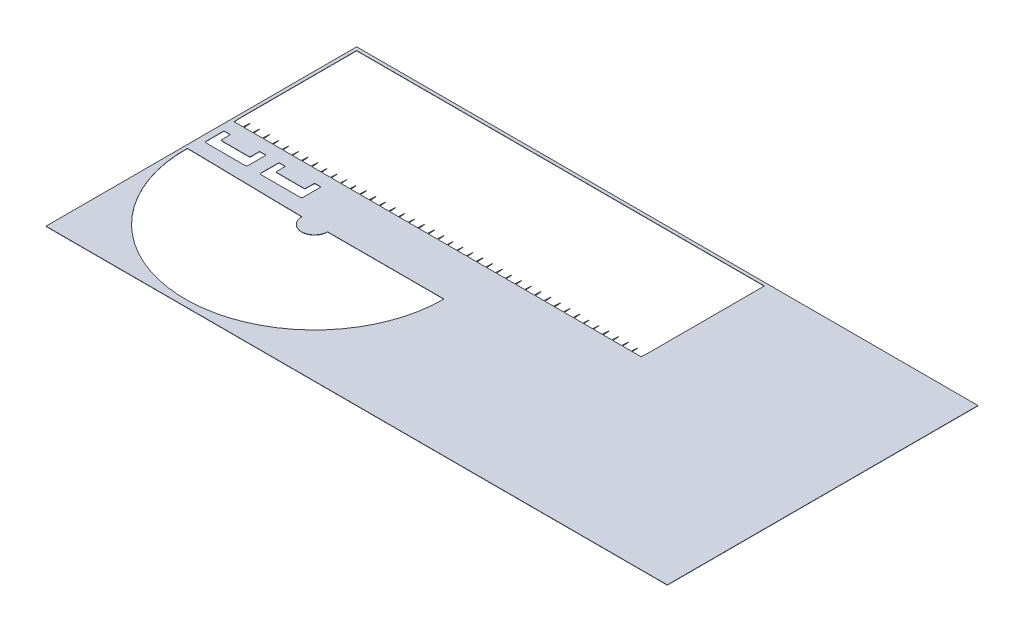
SolidWorks part; units mm, degrees
ref_plane "Front Plane" through (0, 0, 0) normal (0, 0, 1) x (1, 0, 0)
ref_plane "Top Plane" through (0, 0, 0) normal (0, 1, 0) x (1, 0, 0)
ref_plane "Right Plane" through (0, 0, 0) normal (1, 0, 0) x (0, 0, -1)
sketch "Sketch1" plane through (0, 0, 0) normal (0, 1, 0) x (1, 0, 0)
  line L1 (-1219.2, 609.6) -> (1219.2, 609.6)
  line L2 (-1219.2, 609.6) -> (-1219.2, -609.6)
  line L3 (-1219.2, -609.6) -> (1219.2, -609.6)
  line L4 (1219.2, 609.6) -> (1219.2, -609.6)
  line L5 (-1219.2, 609.6) -> (1219.2, -609.6) construction
  line L6 (-1219.2, -609.6) -> (1219.2, 609.6) construction
  point P0 (0, 0)
  dimension "D1" = 1219.2
  dimension "D2" = 2438.4
base flange "Base-Flange1" sketch "Sketch1" thickness 1.0236 reverse thickness direction no parameters "D1"=0.7366
sketch "Sketch6" plane through (0, 0, 0) normal (0, 1, 0) x (1, 0, 0)
  line L0 (1219.2, 609.6) -> (-1219.2, 609.6) construction
  line L1 (-1206.5, 596.9) -> (393.7, 596.9)
  line L2 (-1206.5, 596.9) -> (-1206.5, 139.7)
  line L3 (-1206.5, 139.7) -> (-1204.6839, 114.3)
  line L4 (393.7, 596.9) -> (393.7, 139.7)
  line L5 (-1219.2, 609.6) -> (-1219.2, -609.6) construction
  line L6 (-647.7, -76.2) -> (-190.5, -76.2)
  line L7 (-1206.4226, -67.3342) -> (-749.2923, -75.3134)
  line L8 (-1204.6839, 114.3) -> (-1170.2161, 114.3)
  line L9 (-1170.2161, 114.3) -> (-1168.4, 139.7)
  line L10 (-1168.4, 139.7) -> (-1206.5, 139.7) construction
  line L11 (-1187.45, 139.7) -> (-1187.45, 114.3) construction
  line L12 (-1111.25, -12.7) -> (-1187.45, -12.7)
  line L13 (-1168.4, 139.7) -> (-1166.5839, 114.3)
  line L14 (-1166.5839, 114.3) -> (-1132.1161, 114.3)
  line L15 (-1132.1161, 114.3) -> (-1130.3, 139.7)
  line L16 (-1130.3, 139.7) -> (-1128.4839, 114.3)
  line L17 (-1128.4839, 114.3) -> (-1094.0161, 114.3)
  line L18 (-1094.0161, 114.3) -> (-1092.2, 139.7)
  line L19 (-1092.2, 139.7) -> (-1090.3839, 114.3)
  line L20 (-1090.3839, 114.3) -> (-1055.9161, 114.3)
  line L21 (-1055.9161, 114.3) -> (-1054.1, 139.7)
  line L22 (-1054.1, 139.7) -> (-1052.2839, 114.3)
  line L23 (-1052.2839, 114.3) -> (-1017.8161, 114.3)
  line L24 (-1017.8161, 114.3) -> (-1016, 139.7)
  line L25 (-1016, 139.7) -> (-1014.1839, 114.3)
  line L26 (-1014.1839, 114.3) -> (-979.7161, 114.3)
  line L27 (-979.7161, 114.3) -> (-977.9, 139.7)
  line L28 (-977.9, 139.7) -> (-976.0839, 114.3)
  line L29 (-976.0839, 114.3) -> (-941.6161, 114.3)
  line L30 (-941.6161, 114.3) -> (-939.8, 139.7)
  line L31 (-939.8, 139.7) -> (-937.9839, 114.3)
  line L32 (-937.9839, 114.3) -> (-903.5161, 114.3)
  line L33 (-903.5161, 114.3) -> (-901.7, 139.7)
  line L34 (-901.7, 139.7) -> (-899.8839, 114.3)
  line L35 (-899.8839, 114.3) -> (-865.4161, 114.3)
  line L36 (-865.4161, 114.3) -> (-863.6, 139.7)
  line L37 (-863.6, 139.7) -> (-861.7839, 114.3)
  line L38 (-861.7839, 114.3) -> (-827.3161, 114.3)
  line L39 (-827.3161, 114.3) -> (-825.5, 139.7)
  line L40 (-825.5, 139.7) -> (-823.6839, 114.3)
  line L41 (-823.6839, 114.3) -> (-789.2161, 114.3)
  line L42 (-789.2161, 114.3) -> (-787.4, 139.7)
  line L43 (-787.4, 139.7) -> (-785.5839, 114.3)
  line L44 (-785.5839, 114.3) -> (-751.1161, 114.3)
  line L45 (-751.1161, 114.3) -> (-749.3, 139.7)
  line L46 (-749.3, 139.7) -> (-747.4839, 114.3)
  line L47 (-747.4839, 114.3) -> (-713.0161, 114.3)
  line L48 (-713.0161, 114.3) -> (-711.2, 139.7)
  line L49 (-711.2, 139.7) -> (-709.3839, 114.3)
  line L50 (-709.3839, 114.3) -> (-674.9161, 114.3)
  line L51 (-674.9161, 114.3) -> (-673.1, 139.7)
  line L52 (-673.1, 139.7) -> (-671.2839, 114.3)
  line L53 (-671.2839, 114.3) -> (-636.8161, 114.3)
  line L54 (-636.8161, 114.3) -> (-635, 139.7)
  line L55 (-635, 139.7) -> (-633.1839, 114.3)
  line L56 (-633.1839, 114.3) -> (-598.7161, 114.3)
  line L57 (-598.7161, 114.3) -> (-596.9, 139.7)
  line L58 (-596.9, 139.7) -> (-595.0839, 114.3)
  line L59 (-595.0839, 114.3) -> (-560.6161, 114.3)
  line L60 (-560.6161, 114.3) -> (-558.8, 139.7)
  line L61 (-558.8, 139.7) -> (-556.9839, 114.3)
  line L62 (-556.9839, 114.3) -> (-522.5161, 114.3)
  line L63 (-522.5161, 114.3) -> (-520.7, 139.7)
  line L64 (-520.7, 139.7) -> (-518.8839, 114.3)
  line L65 (-518.8839, 114.3) -> (-484.4161, 114.3)
  line L66 (-484.4161, 114.3) -> (-482.6, 139.7)
  line L67 (-482.6, 139.7) -> (-480.7839, 114.3)
  line L68 (-480.7839, 114.3) -> (-446.3161, 114.3)
  line L69 (-446.3161, 114.3) -> (-444.5, 139.7)
  line L70 (-444.5, 139.7) -> (-442.6839, 114.3)
  line L71 (-442.6839, 114.3) -> (-408.2161, 114.3)
  line L72 (-408.2161, 114.3) -> (-406.4, 139.7)
  line L73 (-406.4, 139.7) -> (-404.5839, 114.3)
  line L74 (-404.5839, 114.3) -> (-370.1161, 114.3)
  line L75 (-370.1161, 114.3) -> (-368.3, 139.7)
  line L76 (-368.3, 139.7) -> (-366.4839, 114.3)
  line L77 (-366.4839, 114.3) -> (-332.0161, 114.3)
  line L78 (-332.0161, 114.3) -> (-330.2, 139.7)
  line L79 (-330.2, 139.7) -> (-328.3839, 114.3)
  line L80 (-328.3839, 114.3) -> (-293.9161, 114.3)
  line L81 (-293.9161, 114.3) -> (-292.1, 139.7)
  line L82 (-292.1, 139.7) -> (-290.2839, 114.3)
  line L83 (-290.2839, 114.3) -> (-255.8161, 114.3)
  line L84 (-255.8161, 114.3) -> (-254, 139.7)
  line L85 (-254, 139.7) -> (-252.1839, 114.3)
  line L86 (-252.1839, 114.3) -> (-217.7161, 114.3)
  line L87 (-217.7161, 114.3) -> (-215.9, 139.7)
  line L88 (-215.9, 139.7) -> (-214.0839, 114.3)
  line L89 (-214.0839, 114.3) -> (-179.6161, 114.3)
  line L90 (-179.6161, 114.3) -> (-177.8, 139.7)
  line L91 (-177.8, 139.7) -> (-175.9839, 114.3)
  line L92 (-175.9839, 114.3) -> (-141.5161, 114.3)
  line L93 (-141.5161, 114.3) -> (-139.7, 139.7)
  line L94 (-139.7, 139.7) -> (-137.8839, 114.3)
  line L95 (-137.8839, 114.3) -> (-103.4161, 114.3)
  line L96 (-103.4161, 114.3) -> (-101.6, 139.7)
  line L97 (-101.6, 139.7) -> (-99.7839, 114.3)
  line L98 (-99.7839, 114.3) -> (-65.3161, 114.3)
  line L99 (-65.3161, 114.3) -> (-63.5, 139.7)
  line L100 (-63.5, 139.7) -> (-61.6839, 114.3)
  line L101 (-61.6839, 114.3) -> (-27.2161, 114.3)
  line L102 (-27.2161, 114.3) -> (-25.4, 139.7)
  line L103 (-25.4, 139.7) -> (-23.5839, 114.3)
  line L104 (-23.5839, 114.3) -> (10.8839, 114.3)
  line L105 (10.8839, 114.3) -> (12.7, 139.7)
  line L106 (12.7, 139.7) -> (14.5161, 114.3)
  line L107 (14.5161, 114.3) -> (48.9839, 114.3)
  line L108 (48.9839, 114.3) -> (50.8, 139.7)
  line L109 (50.8, 139.7) -> (52.6161, 114.3)
  line L110 (52.6161, 114.3) -> (87.0839, 114.3)
  line L111 (87.0839, 114.3) -> (88.9, 139.7)
  line L112 (88.9, 139.7) -> (90.7161, 114.3)
  line L113 (90.7161, 114.3) -> (125.1839, 114.3)
  line L114 (125.1839, 114.3) -> (127, 139.7)
  line L115 (127, 139.7) -> (128.8161, 114.3)
  line L116 (128.8161, 114.3) -> (163.2839, 114.3)
  line L117 (163.2839, 114.3) -> (165.1, 139.7)
  line L118 (165.1, 139.7) -> (166.9161, 114.3)
  line L119 (166.9161, 114.3) -> (201.3839, 114.3)
  line L120 (201.3839, 114.3) -> (203.2, 139.7)
  line L121 (203.2, 139.7) -> (205.0161, 114.3)
  line L122 (205.0161, 114.3) -> (239.4839, 114.3)
  line L123 (239.4839, 114.3) -> (241.3, 139.7)
  line L124 (241.3, 139.7) -> (243.1161, 114.3)
  line L125 (243.1161, 114.3) -> (277.5839, 114.3)
  line L126 (277.5839, 114.3) -> (279.4, 139.7)
  line L127 (279.4, 139.7) -> (281.2161, 114.3)
  line L128 (281.2161, 114.3) -> (315.6839, 114.3)
  line L129 (315.6839, 114.3) -> (317.5, 139.7)
  line L130 (317.5, 139.7) -> (319.3161, 114.3)
  line L131 (319.3161, 114.3) -> (353.7839, 114.3)
  line L132 (353.7839, 114.3) -> (355.6, 139.7)
  line L133 (355.6, 139.7) -> (357.4161, 114.3)
  line L134 (357.4161, 114.3) -> (391.8839, 114.3)
  line L135 (391.8839, 114.3) -> (393.7, 139.7)
  line L136 (-1219.2, -609.6) -> (1219.2, -609.6) construction
  line L137 (-1193.8, -6.35) -> (-1193.8, 60.325)
  line L138 (-1190.625, 63.5) -> (-1171.575, 63.5)
  line L139 (-1168.4, 60.325) -> (-1168.4, 28.575)
  line L140 (-1206.5, 139.7) -> (393.7, 139.7) construction
  line L141 (-1165.225, 25.4) -> (-1057.275, 25.4)
  line L142 (-1054.1, 28.575) -> (-1054.1, 60.325)
  line L143 (-1050.925, 63.5) -> (-1031.875, 63.5)
  line L144 (-1028.7, 60.325) -> (-1028.7, -6.35)
  line L145 (-1035.05, -12.7) -> (-1111.25, -12.7)
  line L146 (-895.35, -12.7) -> (-971.55, -12.7)
  line L147 (-977.9, -6.35) -> (-977.9, 60.325)
  line L148 (-974.725, 63.5) -> (-955.675, 63.5)
  line L149 (-952.5, 60.325) -> (-952.5, 28.575)
  line L150 (-949.325, 25.4) -> (-841.375, 25.4)
  line L151 (-838.2, 28.575) -> (-838.2, 60.325)
  line L152 (-835.025, 63.5) -> (-815.975, 63.5)
  line L153 (-812.8, 60.325) -> (-812.8, -6.35)
  line L154 (-819.15, -12.7) -> (-895.35, -12.7)
  arc A0 (-190.5, -76.2) -> (-1206.4226, -67.3342) centre (-698.5, -76.2) cw
  arc A1 (-749.2923, -75.3134) -> (-647.7, -76.2) centre (-698.5, -76.2) ccw
  arc A2 (-1028.7, -6.35) -> (-1035.05, -12.7) centre (-1035.05, -6.35) cw
  arc A3 (-1187.45, -12.7) -> (-1193.8, -6.35) centre (-1187.45, -6.35) cw
  arc A4 (-1028.7, 60.325) -> (-1031.875, 63.5) centre (-1031.875, 60.325) ccw
  arc A5 (-1054.1, 60.325) -> (-1050.925, 63.5) centre (-1050.925, 60.325) cw
  arc A6 (-1054.1, 28.575) -> (-1057.275, 25.4) centre (-1057.275, 28.575) cw
  arc A7 (-1165.225, 25.4) -> (-1168.4, 28.575) centre (-1165.225, 28.575) cw
  arc A8 (-1168.4, 60.325) -> (-1171.575, 63.5) centre (-1171.575, 60.325) ccw
  arc A9 (-1190.625, 63.5) -> (-1193.8, 60.325) centre (-1190.625, 60.325) ccw
  arc A10 (-812.8, -6.35) -> (-819.15, -12.7) centre (-819.15, -6.35) cw
  arc A11 (-971.55, -12.7) -> (-977.9, -6.35) centre (-971.55, -6.35) cw
  arc A12 (-812.8, 60.325) -> (-815.975, 63.5) centre (-815.975, 60.325) ccw
  arc A13 (-838.2, 60.325) -> (-835.025, 63.5) centre (-835.025, 60.325) cw
  arc A14 (-838.2, 28.575) -> (-841.375, 25.4) centre (-841.375, 28.575) cw
  arc A15 (-949.325, 25.4) -> (-952.5, 28.575) centre (-949.325, 28.575) cw
  arc A16 (-952.5, 60.325) -> (-955.675, 63.5) centre (-955.675, 60.325) ccw
  arc A17 (-974.725, 63.5) -> (-977.9, 60.325) centre (-974.725, 60.325) ccw
  point P77 (-1028.7, 63.5)
  point P89 (-1054.1, 63.5)
  point P101 (-1054.1, 25.4)
  dimension "D6" = 508
  dimension "D14" = 165.1
  dimension "D15" = 38.1
  dimension "D19" = 6.35
  dimension "D20" = 3.175
  dimension "D25" = 6.35
  dimension "D26" = 3.175
  dimension "D2" = 457.2
  dimension "D3" = 12.7
  dimension "D4" = 12.7
  dimension "D5" = 457.2
  dimension "D7" = 181
  dimension "D8" = 38.1
  dimension "D9" = 520.7
  dimension "D10" = 34.4678
  dimension "D11" = 25.4
  dimension "D13" = 533.4
  dimension "D16" = 1600.2
  dimension "D17" = 25.4
  dimension "D18" = 38.1
  dimension "D21" = 25.4
  dimension "D22" = 596.9
  dimension "D23" = 165.1
  dimension "D24" = 38.1
  dimension "D27" = 76.2
  dimension "D28" = 25.4
  dimension "D29" = 50.8
  dimension "D12" = 42
extrude "Cut-Extrude1" cut sketch "Sketch6" against normal through all normal cut yes
sketch "Bend-Lines1" plane through (0, 0, 0) normal (0, 1, 0) x (1, 0, 0)
sketch "Bounding-Box1" plane through (0, 0, 0) normal (0, 1, 0) x (1, 0, 0)
sheet metal parameters "Sheet-Metal(1)" thickness 1.0236 parameters "D1"=0.7366
flat pattern "Flat-Pattern(1)" [suppressed]
sketch "Bend-Lines2" plane through (0, 0, 0) normal (0, 1, 0) x (1, 0, 0)
sketch "Bounding-Box2" [suppressed] plane through (0, 0, 0) normal (0, 1, 0) x (1, 0, 0)
sheet metal parameters "Sheet-Metal(2)" thickness 1.0236 parameters "D1"=0.7366
flat pattern "Flat-Pattern(1)"
sketch "Bend-Lines2" plane through (0, 0, 0) normal (0, 1, 0) x (1, 0, 0)
sketch3d "Bounding-Box2" [suppressed]
  line L0 (1219.2, -609.6, 0) -> (-1219.2, -609.6, 0) construction
  line L1 (1219.2, 609.6, 0) -> (-1219.2, 609.6, 0) construction
  line L2 (1219.2, -609.6, 0) -> (1219.2, 609.6, 0) construction
  line L3 (-1219.2, -609.6, 0) -> (-1219.2, 609.6, 0) construction
